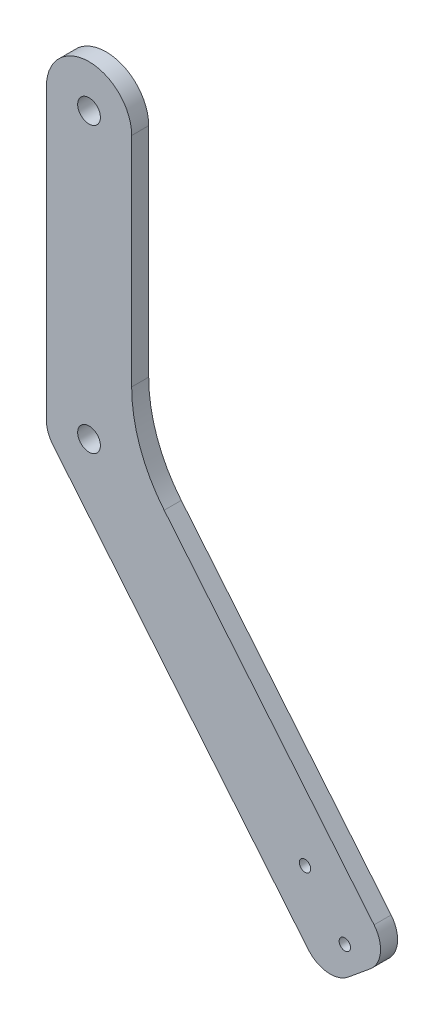
SolidWorks part; units mm, degrees
ref_plane "Front Plane" through (0, 0, 0) normal (0, 0, 1) x (1, 0, 0)
ref_plane "Top Plane" through (0, 0, 0) normal (0, 1, 0) x (1, 0, 0)
ref_plane "Right Plane" through (0, 0, 0) normal (1, 0, 0) x (0, 0, -1)
sketch "Sketch1" plane through (0, 0, 0) normal (0, 0, 1) x (1, 0, 0)
  line L0 (0, 100) -> (0, 0) construction
  line L1 (0, 0) -> (111.0112, -134.4282) construction
  line L2 (106.6585, -105.6002) -> (83.5264, -124.7027)
  line L3 (-15, 115) -> (15, 115)
  line L4 (15, 115) -> (15, 5.3929)
  line L5 (15, 5.3929) -> (106.6585, -105.6002)
  line L6 (83.5264, -124.7027) -> (-15, -5.3929)
  line L7 (-15, -5.3929) -> (-15, 115)
  circle A0 centre (0, 100) radius 4
  circle A1 centre (0, 0) radius 4
  circle A2 centre (75.9899, -92.0194) radius 2
  circle A3 centre (89.9984, -108.9829) radius 2
  point P13 (0, 115)
  point P14 (95.0924, -115.1515)
  dimension "D4" = 8
  dimension "D5" = 8
  dimension "D7" = 4
  dimension "D1" = 140.45
  dimension "D2" = 174.34
  dimension "D3" = 100
  dimension "D6" = 22
  dimension "D8" = 33
  dimension "D9" = 8
  dimension "D10" = 30
  dimension "D11" = 30
  dimension "D12" = 15
extrude "Boss-Extrude1" add sketch "Sketch1" along normal mid plane 6
fillet "Fillet1" 2 edges at (-15, 115, 0) (15, 115, 0) type full round first side face at (-15, 54.8035, 0) second side face at (15, 60.1965, 0) middle face at (0, 115, 0)
fillet "Fillet2" radius 10 3 edges at (106.6585, -105.6002, 0) (83.5264, -124.7027, 0) (-15, -5.3929, 0)
fillet "Fillet3" radius 50 1 edges at (15, 5.3929, 0)
